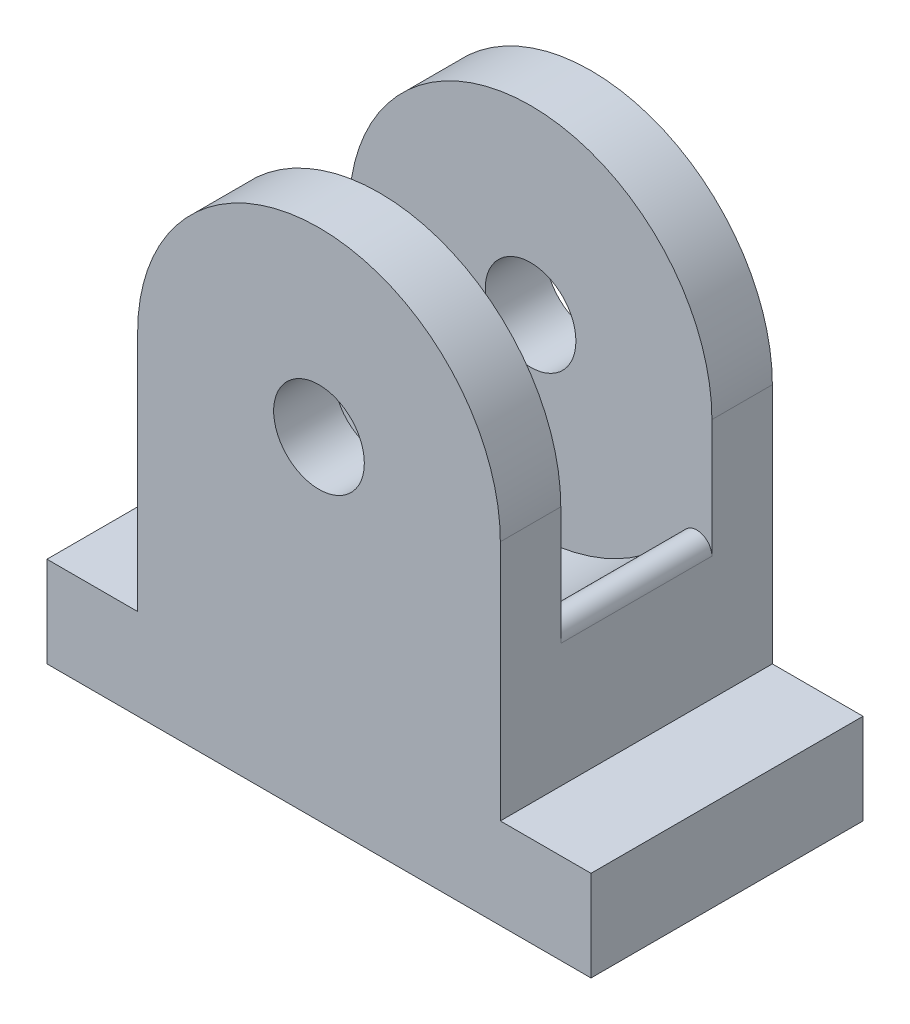
SolidWorks part; units mm, degrees
ref_plane "前视基准面" through (0, 0, 0) normal (0, 0, 1) x (1, 0, 0)
ref_plane "上视基准面" through (0, 0, 0) normal (0, 1, 0) x (1, 0, 0)
ref_plane "右视基准面" through (0, 0, 0) normal (1, 0, 0) x (0, 0, -1)
sketch "草图1" plane through (0, 0, 0) normal (0, 0, 1) x (1, 0, 0)
  line L0 (-6, 0) -> (-6, -8)
  line L1 (6, 0) -> (6, -8)
  line L3 (-6, -8) -> (-9, -8)
  line L4 (-9, -8) -> (-9, -11)
  line L5 (-9, -11) -> (9, -11)
  line L6 (9, -11) -> (9, -8)
  line L7 (9, -8) -> (6, -8)
  arc A0 (6, 0) -> (-6, 0) centre (0, 0) ccw
  circle A1 centre (0, 0) radius 1.5
  dimension "D1" = 12
  dimension "D2" = 3
  dimension "D3" = 8
  dimension "D4" = 8
  dimension "D5" = 3
  dimension "D6" = 3
  dimension "D7" = 3
extrude "凸台-拉伸1" add sketch "草图1" along normal blind 2
sketch "草图2" plane through (0, 0, 2) normal (0, 0, 1) x (1, 0, 0)
  line L0 (-9, -8) -> (9, -8)
  line L1 (9, -8) -> (9, -11)
  line L2 (9, -11) -> (-9, -11)
  line L3 (-9, -11) -> (-9, -8)
extrude "凸台-拉伸2" add sketch "草图2" along normal blind 2.5
sketch "草图3" plane through (0, 0, 0) normal (0, 0, -1) x (-1, 0, 0)
  line L0 (-9, -8) -> (-9, -11)
  line L1 (-9, -11) -> (9, -11)
  line L2 (9, -11) -> (9, -8)
  line L3 (9, -8) -> (-9, -8)
sketch "草图5" plane through (0, 0, 2) normal (0, 0, 1) x (1, 0, 0)
  line L0 (6, -1.75) -> (6, -8)
  line L1 (6, -8) -> (6, 0) construction
  line L2 (6, -8) -> (-6, -8)
  line L3 (-6, -8) -> (-6, -1.75)
  line L4 (-6, 0) -> (-6, -8) construction
  arc A0 (-6, -1.75) -> (6, -1.75) centre (0, 0) ccw
  dimension "D1" = 12.5
extrude "凸台-拉伸3" add sketch "草图5" along normal blind 2.5
fillet "圆角1" radius 0.5 1 edges at (-6, -1.75, 3.25)
fillet "圆角2" radius 0.5 1 edges at (6, -1.75, 3.25)
mirror "镜向3" about plane through (0, 0, 4.5) normal (0, 0, -1) of bodies 110
sketch "草图6" plane through (0, -11, 0) normal (0, -1, 0) x (1, 0, 0)
  line L0 (0, 9) -> (0, 0) construction
  line L1 (-9, 9) -> (9, 9) construction
  line L2 (-9, 0) -> (9, 0) construction
  line L3 (9, 4.5) -> (-9, 4.5) construction
  line L4 (9, 9) -> (9, 0) construction
  line L5 (-9, 9) -> (-9, 0) construction
  circle A0 centre (0, 4.5) radius 1.35
  dimension "D1" = 2.7
extrude "切除-拉伸1" cut sketch "草图6" against normal blind 10 and the other way through all
ref_point "点1"
ref_point "点2"
ref_axis "基准轴1" through (0, 0, 7) along (0, 0, -1)
ref_axis "基准轴2" through (0, -11, 4.5) along (0, 1, 0)
